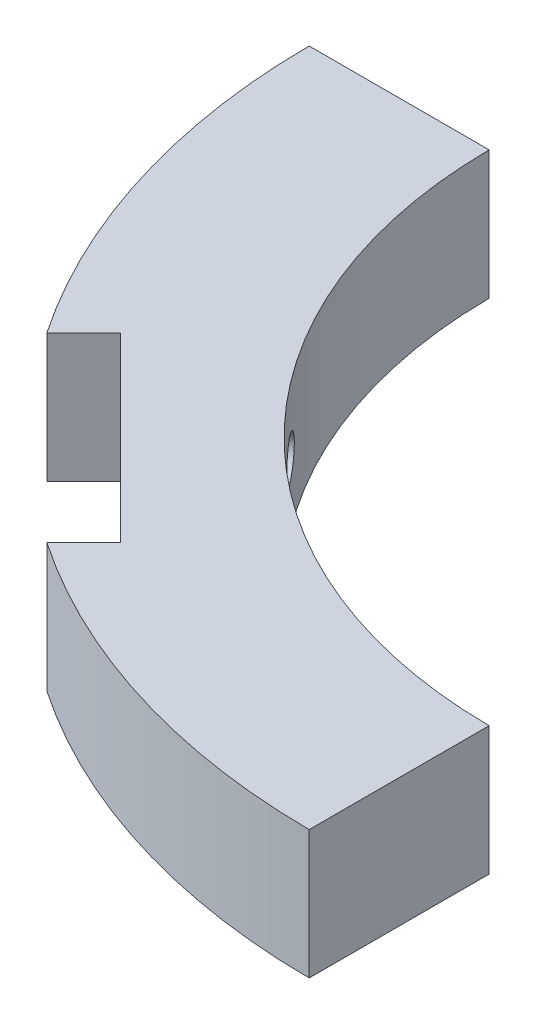
SolidWorks part; units mm, degrees
material "6061-T6 (SS)"
ref_plane "Front Plane" through (0, 0, 0) normal (0, 0, 1) x (1, 0, 0)
ref_plane "Top Plane" through (0, 0, 0) normal (0, 1, 0) x (1, 0, 0)
ref_plane "Right Plane" through (0, 0, 0) normal (1, 0, 0) x (0, 0, -1)
sketch "Sketch1" plane through (0, 0, 0) normal (0, 1, 0) x (1, 0, 0)
  line L0 (0, 0) -> (-24.5, 0) construction
  line L1 (0, 0) -> (0, -24.5) construction
  line L2 (-19.4997, -0.1) -> (-26.4998, -0.1)
  line L3 (-0.1, -19.4997) -> (-0.1, -26.4998)
  line L4 (-0.1, -0.1) -> (-24.5, -0.1) construction
  line L5 (-0.1, -0.1) -> (-0.1, -24.5) construction
  arc A0 (-19.4997, -0.1) -> (-0.1, -19.4997) centre (0, 0) ccw
  arc A1 (-26.4998, -0.1) -> (-0.1, -26.4998) centre (0, 0) ccw
  dimension "D1" = 39
  dimension "D2" = 53
  dimension "D3" = 0.1
extrude "Boss-Extrude1" add sketch "Sketch1" along normal mid plane 5
sketch "Sketch2" plane through (0, 2.5, 0) normal (0, 1, 0) x (1, 0, 0)
  line L0 (-18.7383, -18.7383) -> (0, 0) construction
  line L1 (-22.2739, -15.2028) -> (-15.2028, -22.2739)
  line L5 (-22.2739, -15.2028) -> (-20.5061, -13.435)
  line L6 (-20.5061, -13.435) -> (-13.435, -20.5061)
  line L7 (-13.435, -20.5061) -> (-15.2028, -22.2739)
  arc A0 (-26.4998, -0.1) -> (-0.1, -26.4998) centre (0, 0) ccw construction
  point P9 (-18.7383, -18.7383)
  dimension "D1" = 2.5
  dimension "D2" = 10
extrude "Cut-Extrude1" cut sketch "Sketch2" against normal through all
sketch "Sketch3" plane through (-16.9706, 0, 16.9706) normal (-0.7071, 0, 0.7071) x (0.7071, 0, 0.7071)
  line L0 (-5, 0) -> (5, 0) construction
  line L1 (-5, -2.5) -> (-5, 2.5) construction
  line L2 (5, 2.5) -> (5, -2.5) construction
  line L3 (0, 0) -> (0, 2.5) construction
  line L4 (5, 2.5) -> (-5, 2.5) construction
  point P6 (-2.5, 0)
  point P12 (2.5, 0)
  dimension "D1" = 2.5
hole_wizard "Tap Drill for M2x0.4 Tap1" positions "3DSketch1" profile "Sketch4" hole size "M2x0.4" standard "ANSI Metric" end condition through all
sketch3d "3DSketch1"
  point P0 (-18.7383, 0, 15.2028)
  point P3 (-15.2028, 0, 18.7383)
sketch "Sketch4" plane through (-18.7383, 0, 15.2028) normal (0, 1, 0) x (0.7071, 0, 0.7071)
  line L0 (0, 0) -> (0, 23.8586)
  line L1 (0, 23.8586) -> (0.8, 23.8586)
  line L2 (0.8, 23.8586) -> (0.8, 0)
  line L5 (0.8, 0) -> (0, 0)
  line L11 (0, -6.35) -> (0, 107.95) construction
  dimension "Thru Hole Dia." = 1.6
  dimension "Thru Hole Depth" = 23.8586
thread "Thread1" pitch 0.4 method extrude profile "Thread Profile1" start angle 0, offset 0, length 2.3, pitch 0.4, diameter 1.6
ref_plane "Plane1" through (-19.304, 0, 14.6371) normal (0, -1, 0) x (-0.7071, 0, -0.7071)
sketch "Thread Profile1" plane through (-19.304, 0, 14.6371) normal (0, -1, 0) x (-0.7071, 0, -0.7071)
  line L0 (0, 0) -> (0, 0.4) construction
  line L11 (0, 0) -> (0, 0.35)
  line L12 (0, 0.35) -> (-0.2165, 0.225)
  line L13 (-0.2165, 0.225) -> (-0.2165, 0.125)
  line L15 (-0.2165, 0.125) -> (0, 0)
  line L17 (-0.2165, 0.175) -> (0, 0.175) construction
  point P2 (0, 0)
  dimension "Pitch" = 0.4
  dimension "Profile_Angle" = 60
  dimension "Profile_Land" = 0.1
  dimension "Profile_Height" = 0.2165
thread "Thread2" pitch 0.4 method extrude profile "Thread Profile2" start angle 0, offset 0, length 2.3, pitch 0.4, diameter 1.6
ref_plane "Plane2" through (-15.7685, 0, 18.1726) normal (0, -1, 0) x (-0.7071, 0, -0.7071)
sketch "Thread Profile2" plane through (-15.7685, 0, 18.1726) normal (0, -1, 0) x (-0.7071, 0, -0.7071)
  line L0 (0, 0) -> (0, 0.4) construction
  line L11 (0, 0) -> (0, 0.35)
  line L12 (0, 0.35) -> (-0.2165, 0.225)
  line L13 (-0.2165, 0.225) -> (-0.2165, 0.125)
  line L15 (-0.2165, 0.125) -> (0, 0)
  line L17 (-0.2165, 0.175) -> (0, 0.175) construction
  point P2 (0, 0)
  dimension "Pitch" = 0.4
  dimension "Profile_Angle" = 60
  dimension "Profile_Land" = 0.1
  dimension "Profile_Height" = 0.2165
